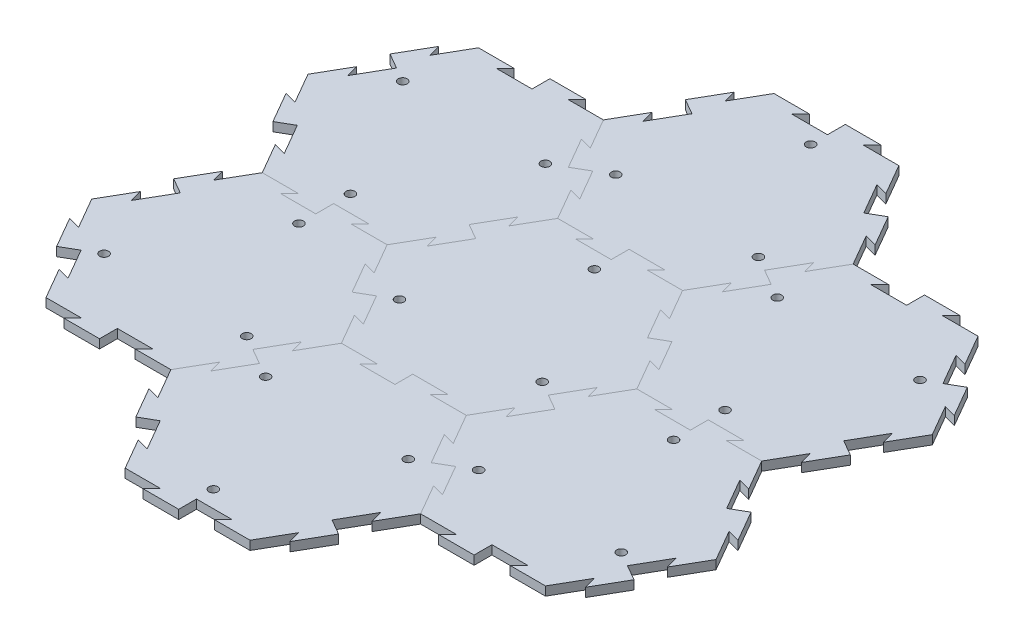
SolidWorks part; units mm, degrees
note: '?' marks a value the reader was unsure of.
material "Cedar"
ref_plane "Front Plane" through (0, 0, 0) normal (0, 0, 1) x (1, 0, 0)
ref_plane "Top Plane" through (0, 0, 0) normal (0, 1, 0) x (1, 0, 0)
ref_plane "Right Plane" through (0, 0, 0) normal (1, 0, 0) x (0, 0, -1)
sketch "Sketch1" plane through (0, 0, 0) normal (0, 1, 0) x (1, 0, 0)
  line L0 (0, 0) -> (88.9, 0) construction
  line L1 (88.9, 0) -> (44.45, 76.9897)
  line L2 (44.45, 76.9897) -> (-44.45, 76.9897)
  line L3 (-44.45, 76.9897) -> (-88.9, 0)
  line L4 (-88.9, 0) -> (-44.45, -76.9897)
  line L5 (-44.45, -76.9897) -> (44.45, -76.9897)
  line L6 (44.45, -76.9897) -> (88.9, 0)
  circle A0 centre (0, 0) radius 76.9897 construction
  dimension "D1" = 88.9
extrude "Boss-Extrude1" add sketch "Sketch1" against normal blind 6.35
sketch "Sketch2" plane through (0, 0, 0) normal (0, 1, 0) x (1, 0, 0)
  point P1 (0, 0)
ref_axis "Axis1" through (0, 0, 0) along (0, 1, 0)?
sketch "Sketch9" plane through (0, 0, 0) normal (0, 1, 0) x (1, 0, 0)
  line L1 (50.8, -29.3294) -> (0, 58.6588) construction
  line L2 (0, 58.6588) -> (-50.8, -29.3294) construction
  line L3 (-50.8, -29.3294) -> (50.8, -29.3294) construction
  circle A0 centre (0, 0) radius 29.3294 construction
  circle A1 centre (-50.8, -29.3294) radius 3.175
  dimension "D2" = 6.35
  dimension "D1" = 101.6
extrude "Cut-Extrude3" cut sketch "Sketch9" against normal through all
pattern_circular "CirPattern6" count 3 over 360 about axis through (0, 0, 0) along (0, 1, 0) of "Cut-Extrude3"
sketch "Sketch10" plane through (0, 0, 0) normal (0, 1, 0) x (1, 0, 0)
  line L0 (44.45, 76.9897) -> (57.15, 54.9926) construction
  line L1 (57.15, 54.9926) -> (48.4757, 57.3169)
  line L2 (48.4757, 57.3169) -> (61.1757, 35.3198)
  line L3 (61.1757, 35.3198) -> (66.675, 38.4948)
  line L4 (57.15, 54.9926) -> (66.675, 38.4948)
  line L5 (88.9, 0) -> (44.45, 76.9897) construction
  dimension "D1" = 45
  dimension "D2" = 6.35
extrude "Cut-Extrude4" cut sketch "Sketch10" against normal through all
sketch "Sketch11" plane through (0, 0, 0) normal (0, 1, 0) x (1, 0, 0)
  line L0 (66.675, 38.4948) -> (88.9, 0) construction
  line L1 (66.675, 38.4948) -> (72.1743, 41.6698)
  line L2 (72.1743, 41.6698) -> (84.8743, 19.6728)
  line L3 (84.8743, 19.6728) -> (76.2, 21.997)
  line L4 (76.2, 21.997) -> (66.675, 38.4948)
  line L5 (76.2, 21.997) -> (88.9, 0) construction
  line L6 (76.2, 21.997) -> (88.9, 0) construction
  line L7 (88.9, 0) -> (66.675, 38.4948) construction
  line L8 (44.45, -76.9897) -> (88.9, 0) construction
  dimension "D1" = 45
  dimension "D2" = 6.35
extrude "Boss-Extrude4" add sketch "Sketch11" against normal blind 6.35 contours L1 L2 L3 L4
pattern_circular "CirPattern7" count 6 over 360 about axis through (0, 0, 0) along (0, 1, 0) of "Cut-Extrude4", "Boss-Extrude4"
pattern_linear "LPattern1" count 2 spacing 153.9793 along (0.866, 0, 0.5) of bodies 125
pattern_circular "CirPattern8" count 6 over 360 about axis through (0, 0, 0) along (0, 1, 0) of bodies 130
